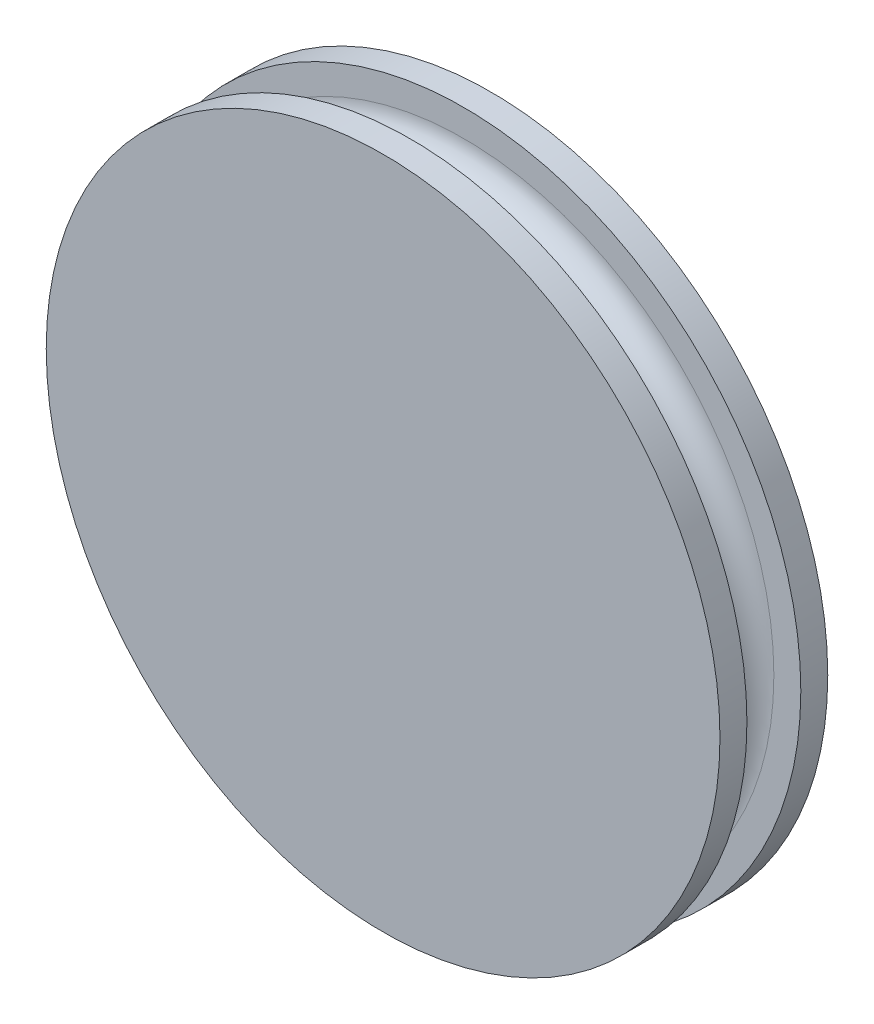
SolidWorks part; units mm, degrees
ref_plane "Front Plane" through (0, 0, 0) normal (0, 0, 1) x (1, 0, 0)
ref_plane "Top Plane" through (0, 0, 0) normal (0, 1, 0) x (1, 0, 0)
ref_plane "Right Plane" through (0, 0, 0) normal (1, 0, 0) x (0, 0, -1)
sketch "Sketch2" plane through (0, 0, 0) normal (0, 0, 1) x (1, 0, 0)
  line L0 (0, 0) -> (0, -3) construction
  line L1 (-1.25, -3) -> (1.25, -3)
  arc A0 (1.25, -3) -> (-1.25, -3) centre (0, 0) ccw
  circle A1 centre (0, 0) radius 5.75
extrude "Boss-Extrude1" add sketch "Sketch2" along normal blind 7.5
sketch "Sketch3" plane through (0, -3, 0) normal (0, 1, 0) x (1, 0, 0)
  line L0 (0, -7.5) -> (0, 0) construction
  line L1 (-1.25, -7.5) -> (1.25, -7.5) construction
  line L2 (-1.25, 0) -> (1.25, 0) construction
  circle A0 centre (0, -3.75) radius 1.5
extrude "Cut-Extrude1" cut sketch "Sketch3" against normal through all and the other way blind 2
sketch "Sketch4" plane through (0, 0, 7.5) normal (0, 0, 1) x (1, 0, 0)
  circle A0 centre (0, 0) radius 62.5
extrude "Boss-Extrude2" add sketch "Sketch4" along normal blind 5
sketch "Sketch5" plane through (0, 0, 12.5) normal (0, 0, 1) x (1, 0, 0)
  circle A2 centre (0, 0) radius 52.5
  circle A3 centre (0, 0) radius 52.5
  dimension "D1" = 10
extrude "Boss-Extrude3" add sketch "Sketch5" along normal blind 10
sketch "Sketch6" plane through (0, 0, 22.5) normal (0, 0, 1) x (1, 0, 0)
  circle A2 centre (0, 0) radius 62.5
  circle A3 centre (0, 0) radius 62.5
  dimension "D1" = 10
extrude "Boss-Extrude4" add sketch "Sketch6" along normal blind 5
fillet "Fillet2" radius 5 2 edges at (52.5, 0, 12.5) (52.5, 0, 22.5)
